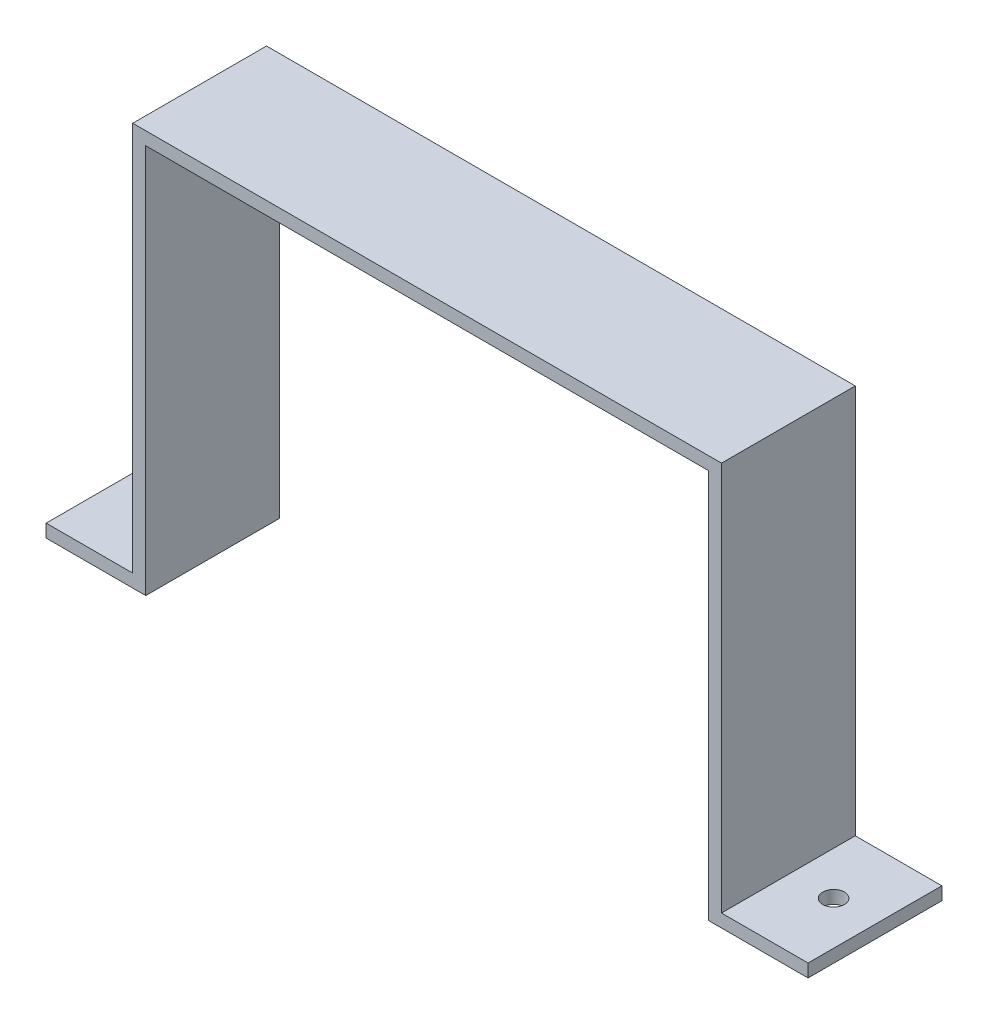
SolidWorks part; units mm, degrees
ref_plane "Płaszczyzna przednia" through (0, 0, 0) normal (0, 0, 1) x (1, 0, 0)
ref_plane "Płaszczyzna górna" through (0, 0, 0) normal (0, 1, 0) x (1, 0, 0)
ref_plane "Płaszczyzna prawa" through (0, 0, 0) normal (1, 0, 0) x (0, 0, -1)
sketch "Sketch1" plane through (0, 0, 0) normal (0, 0, 1) x (1, 0, 0)
  line L1 (3, 0) -> (133, 0)
  line L2 (0, 0) -> (0, 3)
  line L3 (0, 3) -> (136, 3)
  line L4 (136, 0) -> (136, 3)
  line L5 (0, 0) -> (136, 3) construction
  line L6 (0, 3) -> (68, 1.5) construction
  line L8 (0, 0) -> (0, -87)
  line L9 (0, -90) -> (3, -90)
  line L10 (3, 0) -> (3, -90)
  line L11 (0, 0) -> (3, -90) construction
  line L12 (0, -90) -> (3, 0) construction
  line L14 (136, 0) -> (136, -87)
  line L15 (136, -90) -> (133, -90)
  line L16 (133, 0) -> (133, -90)
  line L17 (136, 0) -> (133, -90) construction
  line L18 (134.5, -45) -> (133, 0) construction
  line L19 (0, -90) -> (-20, -90)
  line L21 (0, -87) -> (-20, -87)
  line L22 (-20, -90) -> (-20, -87)
  line L23 (0, -90) -> (-20, -87) construction
  line L24 (0, -87) -> (-20, -90) construction
  line L25 (136, -90) -> (156, -90)
  line L27 (136, -87) -> (156, -87)
  line L28 (156, -90) -> (156, -87)
  line L29 (136, -90) -> (156, -87) construction
  line L30 (136, -87) -> (156, -90) construction
  point P4 (68, 1.5)
  point P9 (1.5, -45)
  point P13 (134.5, -45)
  point P17 (-10, -88.5)
  point P21 (146, -88.5)
  dimension "D1" = 136
  dimension "D2" = 3
  dimension "D3" = 90
  dimension "D4" = 3
  dimension "D5" = 3
  dimension "D6" = 90
  dimension "D7" = 3
  dimension "D8" = 20
  dimension "D9" = 3
  dimension "D10" = 20
extrude "Boss-Extrude1" add sketch "Sketch1" along normal blind 30.9
hole_wizard "Ø5.0mm Dowel Hole1" positions "Sketch2" profile "Sketch3" hole size "Ø5.0" standard "ANSI Metric" end condition up to next
sketch "Sketch2" plane through (0, -87, 0) normal (0, 1, 0) x (1, 0, 0)
  line L0 (-20, -30.9) -> (-20, 0) construction
  line L1 (0, 0) -> (-20, 0) construction
  line L2 (156, -30.9) -> (156, 0) construction
  line L3 (156, 0) -> (136, 0) construction
  point P0 (-10, -15)
  point P2 (146, -15)
  dimension "D1" = 10
  dimension "D2" = 15
  dimension "D3" = 10
  dimension "D4" = 15
sketch "Sketch3" plane through (-10, -87, 15) normal (1, 0, 0) x (0, 0, 1)
  line L0 (0, 0) -> (0, 3)
  line L1 (0, 3) -> (2.5, 3)
  line L2 (2.5, 3) -> (2.5, 0)
  line L5 (2.5, 0) -> (0, 0)
  line L11 (0, -6.35) -> (0, 107.95) construction
  dimension "Thru Hole Dia." = 5
  dimension "Thru Hole Depth" = 3
